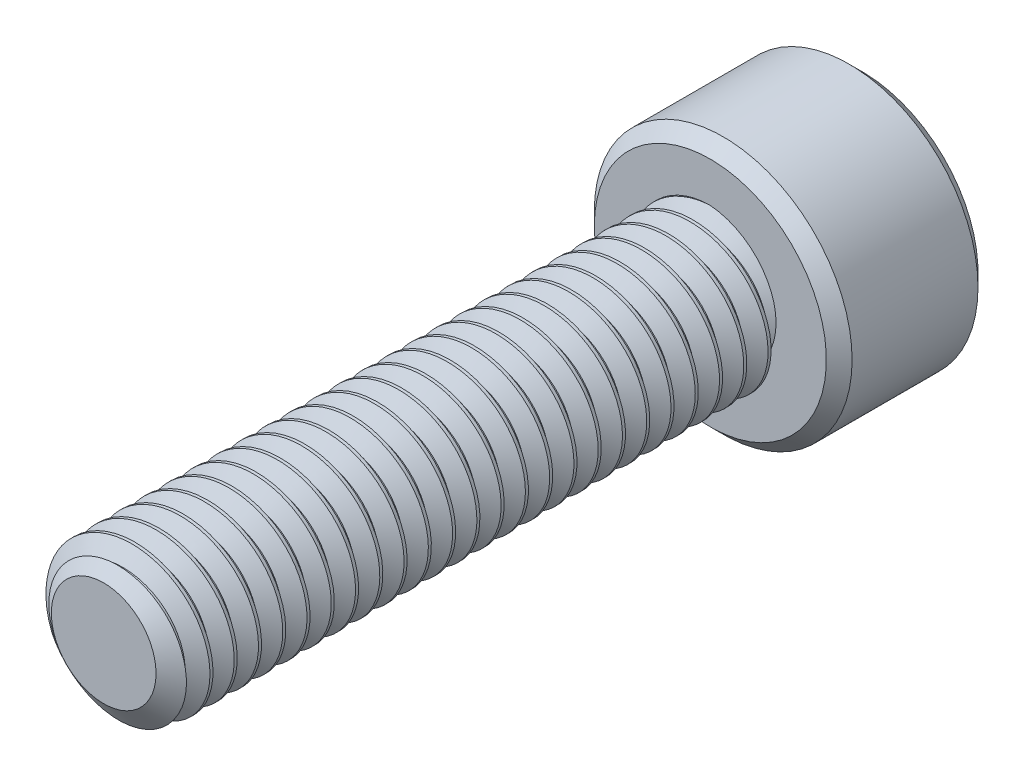
SolidWorks part; units mm, degrees
note: '?' marks a value the reader was unsure of.
other "DetailItem1"
ref_plane "Front Plane" through (0, 0, 0) normal (0, 0, 1) x (1, 0, 0)
ref_plane "Top Plane" through (0, 0, 0) normal (0, 1, 0) x (1, 0, 0)
ref_plane "Right Plane" through (0, 0, 0) normal (1, 0, 0) x (0, 0, -1)
sketch "Sketch1" plane through (0, 0, 0) normal (0, 0, 1) x (1, 0, 0)
  circle A0 centre (0, 0) radius 2.5
  dimension "OD" = 5
extrude "Extrude1" add sketch "Sketch1" against normal blind 20
sketch "Sketch2" plane through (0, 0, 0) normal (0, 0, 1) x (1, 0, 0)
  circle A0 centre (0, 0) radius 2.5 construction
  circle A1 centre (0, 0) radius 2.5
curve "Helix/Spiral1" pitch 0.8 height 20.8 turns 26 parameters "pitch"=0.8
sketch "Sketch3" plane through (0, 0, 0) normal (1, 0, 0) x (0, 0, -1)
  line L0 (-0.7, 2.5) -> (-0.4, 1.9804)
  line L1 (-0.4, 1.9804) -> (-0.3, 1.9804)
  line L2 (-0.3, 1.9804) -> (0, 2.5)
  line L3 (-0.7, 2.5) -> (0, 2.5)
  line L4 (-0.35, 2.5) -> (-0.35, 1.9804) construction
  line L5 (-0.55, 2.2402) -> (-0.15, 2.2402) construction
  line L6 (0, 2.5) -> (0, -2.5) construction
  dimension "D1" = 0.1
  dimension "D2" = 0.4
  dimension "D3" = 60
sweep "Cut-Sweep1" cut profiles "Sketch3" path "Helix/Spiral1"
sketch "Sketch4" plane through (0, 0, 0) normal (1, 0, 0) x (0, 0, -1)
  line L0 (0.5417, 2.5) -> (0, 1.7264)
  line L1 (0, 1.7264) -> (0, 2.5)
  line L2 (0.5417, 2.5) -> (0, 2.5)
  line L3 (-0.7, 2.5) -> (0, 2.5) construction
  line L4 (0, 0) -> (7.0209, 0) construction
  dimension "D1" = 55
  dimension "D2" = 0.254
revolve "Cut-Revolve1" cut sketch "Sketch4" angle 360 about L4
sketch "Sketch6" plane through (0, 0, -20) normal (0, 0, -1) x (-1, 0, 0)
  circle A0 centre (0, 0) radius 4.25
  dimension "head dia" = 8.5
extrude "Extrude2" add sketch "Sketch6" along normal blind 5
sketch "Sketch7" plane through (0, 0, -25) normal (0, 0, -1) x (-1, 0, 0)
  line L1 (0, 2.3094) -> (-2, 1.1547)
  line L2 (-2, 1.1547) -> (-2, -1.1547)
  line L3 (-2, -1.1547) -> (0, -2.3094)
  line L4 (0, -2.3094) -> (2, -1.1547)
  line L5 (2, -1.1547) -> (2, 1.1547)
  line L6 (2, 1.1547) -> (0, 2.3094)
  circle A0 centre (0, 0) radius 2 construction
  dimension "hex dia" = 4
extrude "Cut-Extrude1" cut sketch "Sketch7" against normal blind 3
sketch "Sketch8" plane through (0, 0, -25) normal (0, 0, -1) x (-1, 0, 0)
  circle A0 centre (0, 0) radius 2.3094
extrude "Cut-Extrude2" cut sketch "Sketch8" against normal through all draft 45
chamfer "Chamfer1" distance 0.425 angle 45 2 edges at (-4.25, 0, -25) (-4.25, 0, -20)
sketch "Sketch10" plane through (0, 0, -20) normal (0, 0, 1) x (1, 0, 0)
  circle A1 centre (0, 0) radius 2.5
  circle A2 centre (0, 0) radius 2.5
  dimension "D1" = 0
ref_plane "Plane1" through (0, 0, 0) normal (0, 0, 1) x (1, 0, 0)
extrude "partial thread" [suppressed] add sketch "Sketch10" along normal up to surface (36 mm away) separate body
chamfer "Chamfer2" [suppressed] distance 0.1 angle 45
combine bodies "Combine1" [suppressed] operation type? add bodies to combine 107 108
sketch "Sketch9" plane through (0, 0, 0) normal (1, 0, 0) x (0, 0, -1)
  line L0 (0, 2.5) -> (0, -2.5) construction
  line L1 (2, 2.5) -> (2, -2.5) construction
  dimension "D1" = 2
equation "\"D3@Helix/Spiral1\" = \"screw length@Extrude1\"+\"pitch@Helix/Spiral1\""
equation "\"D1@Sketch3\" = \"pitch@Helix/Spiral1\"*.125"
equation "\"D2@Sketch3\" = \"pitch@Helix/Spiral1\"*.5"
equation "\"D1@Cut-Extrude1\" = \"hex dia@Sketch7\"*.75"
equation "\"D1@Chamfer1\" = \"head dia@Sketch6\"*.05"
equation "\"D1@Sketch9\" = \"pitch@Helix/Spiral1\"*2.5"
equation "\"D1@Chamfer2\"=\"OD@Sketch1\"*.02"
